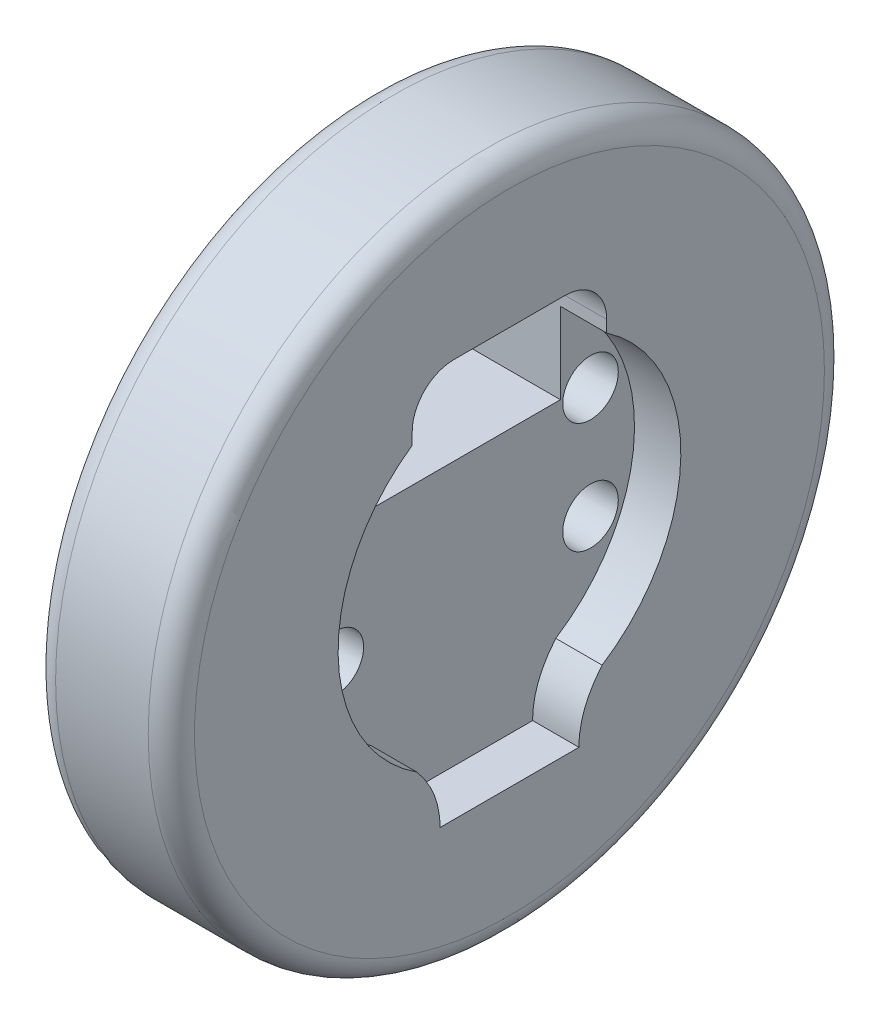
SolidWorks part; units mm, degrees
note: The reader was unsure of these and kept them because the rebuilt part matched: shared geometry of "Sketch4<3>", "Sketch5<4>".
ref_plane "Front Plane" through (0, 0, 0) normal (0, 0, 1) x (1, 0, 0)
ref_plane "Top Plane" through (0, 0, 0) normal (0, 1, 0) x (1, 0, 0)
ref_plane "Right Plane" through (0, 0, 0) normal (1, 0, 0) x (0, 0, -1)
sketch "Sketch2" plane through (0, 0, 0) normal (1, 0, 0) x (0, 0, -1)
  circle A0 centre (0, 0) radius 36.5
  dimension "D1" = 73
extrude "Boss-Extrude1" add sketch "Sketch2" against normal blind 15
sketch "Sketch3" plane through (0, 0, 0) normal (1, 0, 0) x (0, 0, -1)
  line L0 (-7.5, -22) -> (7.5, -22)
  line L1 (-10, -15.5644) -> (-7.5, -18.5) construction
  line L2 (-7.5, -18.5) -> (-7.5, -22) construction
  line L3 (0, -22) -> (0, -18.5)
  line L6 (10, -15.5644) -> (7.5, -18.5) construction
  line L7 (7.5, -18.5) -> (7.5, -22) construction
  circle A2 centre (0, 0) radius 18.5
  spline S0 degree 2 poles (-10, -15.5644) (-7.5, -18.5) (-7.5, -22) knots 0 0 0 1 1 1
  spline S2 degree 2 poles (10, -15.5644) (7.5, -18.5) (7.5, -22) knots 0 0 0 1 1 1
  dimension "D1" = 37
  dimension "D6" = 20
  dimension "D2" = 3.5
  dimension "D3" = 3.5
  dimension "D4" = 7.5
  dimension "D5" = 15
extrude "Cut-Extrude1" cut sketch "Sketch3" against normal offset from surface (5 mm away) 10
sketch "Sketch4" plane through (-5, 0, 0) normal (1, 0, 0) x (0, 0, -1)
  line L0 (13.7477, 6) -> (-13.7477, -6)
  line L1 (-6, 21) -> (10.5, 21)
  line L2 (-10.5, 16.5) -> (-10.5, 6.5)
  line L3 (-10.5, 6.5) -> (10.5, 6.5)
  line L4 (10.5, 21) -> (10.5, 6.5)
  line L5 (-10.5, 21) -> (10.5, 6.5) construction
  line L6 (-10.5, 6.5) -> (10.5, 21) construction
  line L7 (-13.7477, 6) -> (13.7477, -6)
  line L8 (13.7477, 6) -> (13.7477, -6)
  line L9 (-13.7477, 6) -> (-13.7477, -6)
  line L10 (-13.7477, 6) -> (13.7477, 6)
  line L11 (-13.7477, -6) -> (13.7477, -6)
  line L12 (0, 21) -> (0, 6.5)
  line L13 (-10.5, 16.5) -> (-10.5, 21)
  line L14 (-10.5, 21) -> (-6, 21)
  arc A1 (-6, 21) -> (-10.5, 16.5) centre (-6, 16.5) ccw
  circle A2 centre (-13.7477, 6) radius 3
  circle A3 centre (13.7477, 6) radius 3
  circle A4 centre (13.7477, -6) radius 3
  circle A5 centre (-13.7477, -6) radius 3
  arc A6 (6, 21) -> (10.5, 16.5) centre (6, 16.5) cw
  point P0 (0, 13.75)
  point P18 (0, 0)
  arc M5 (10, -15.5644) -> (-10, -15.5644) centre (0, 0) ccw
  dimension "D3" = 6.5
  dimension "D4" = 6
  dimension "D7" = 4.5
  dimension "D1" = 14.5
  dimension "D2" = 21
  dimension "D5" = 30
  dimension "D6" = 12
extrude "Cut-Extrude2" cut sketch "Sketch4" against normal through all and the other way blind 10 contours L4 L2 L3 M5 | L12 L2 L3 M5 | L1 A1 L2 L12 M5 | A6 L1 L12 L4 M5
extrude "Cut-Extrude4" cut sketch "Sketch4<3>" against normal up to surface (10 mm away) draft 1 contours L10 A2 L9 | L9 A2 L7 | L7 A2 L10 | L9 A5 L11 | L0 A5 L9 | L11 A5 L0 | L8 A3 L10 | L10 A3 L0 | L0 A3 L8 | L11 A4 L8 | L8 A4 L7 | L7 A4 L11
sketch "Sketch4<3>" plane through (-5, 0, 0) normal (1, 0, 0) x (0, 0, -1) same geometry as "Sketch4"
sketch "Sketch5" plane through (-15, 0, 0) normal (-1, 0, 0) x (0, 0, 1)
  line L0 (-1.3, 0) -> (-1.3, -1)
  line L1 (-1.3, -1) -> (1.3, -1)
  line L2 (1.3, -1) -> (1.3, 0)
  line L3 (1.3, -1) -> (5, -1)
  line L4 (5, -1) -> (5, 1.3)
  line L5 (5, 1.3) -> (0, 1.3)
  line L6 (-1, -5) -> (1.3, -5)
  line L7 (-1, -1.3) -> (-1, -5)
  line L8 (1.3, -5) -> (1.3, 0)
  line L9 (-5, 1) -> (-5, -1.3)
  line L10 (-1.3, 1) -> (-5, 1)
  line L11 (-5, -1.3) -> (0, -1.3)
  line L12 (1, 5) -> (-1.3, 5)
  line L13 (1, 1.3) -> (1, 5)
  line L14 (-1.3, 5) -> (-1.3, 0)
  line L15 (0, -1.3) -> (0, -1)
  line L16 (0, -1.3) -> (1.3, -1.3)
  arc A1 (1.3, 0) -> (-1.3, 0) centre (0, 0) ccw
  point P24 (0, 0)
  point P25 (0, 0)
  dimension "D1" = 2.6
  dimension "D2" = 1
  dimension "D3" = 5
  dimension "D4" = 4
extrude "Extrude-Thin1" add sketch "Sketch5" along normal blind 4 and the other way up to surface (10 mm away) separate body thin contours A1 L0 L1 L2
extrude "Boss-Extrude8" add sketch "Sketch5<4>" along normal blind 4 and the other way up to surface (10 mm away) separate body
sketch "Sketch5<4>" plane through (-15, 0, 0) normal (-1, 0, 0) x (0, 0, 1) same geometry as "Sketch5"
sketch "Sketch10" plane through (-15, 0, 0) normal (-1, 0, 0) x (0, 0, 1)
  line L0 (1.3, -1) -> (1.3, 0) construction
  line L1 (-1.3, 0) -> (-1.3, -1) construction
  line L2 (-1.3, -1) -> (1.3, -1) construction
  line L3 (1.3, -1) -> (1.3, 0)
  line L4 (-1.3, 0) -> (-1.3, -1)
  line L5 (-1.3, -1) -> (1.3, -1)
  arc A0 (1.3, 0) -> (-1.3, 0) centre (0, 0) ccw construction
  arc A1 (1.3, 0) -> (-1.3, 0) centre (0, 0) ccw
extrude "Cut-Extrude5" cut sketch "Sketch10" against normal offset from surface (6 mm away) 4 up to face at (-5, -6, 10.7477)
sketch "Sketch8" plane through (-5, 0, 0) normal (-1, 0, 0) x (0, 0, 1)
  point P0 (0, 0)
sketch "Sketch9" plane through (-5, 0, 0) normal (1, 0, 0) x (0, 0, -1)
  point P0 (0, 0)
fillet "Fillet1" radius 2.5 2 edges at (0, 0, -36.5) (-15, 0, -36.5)
